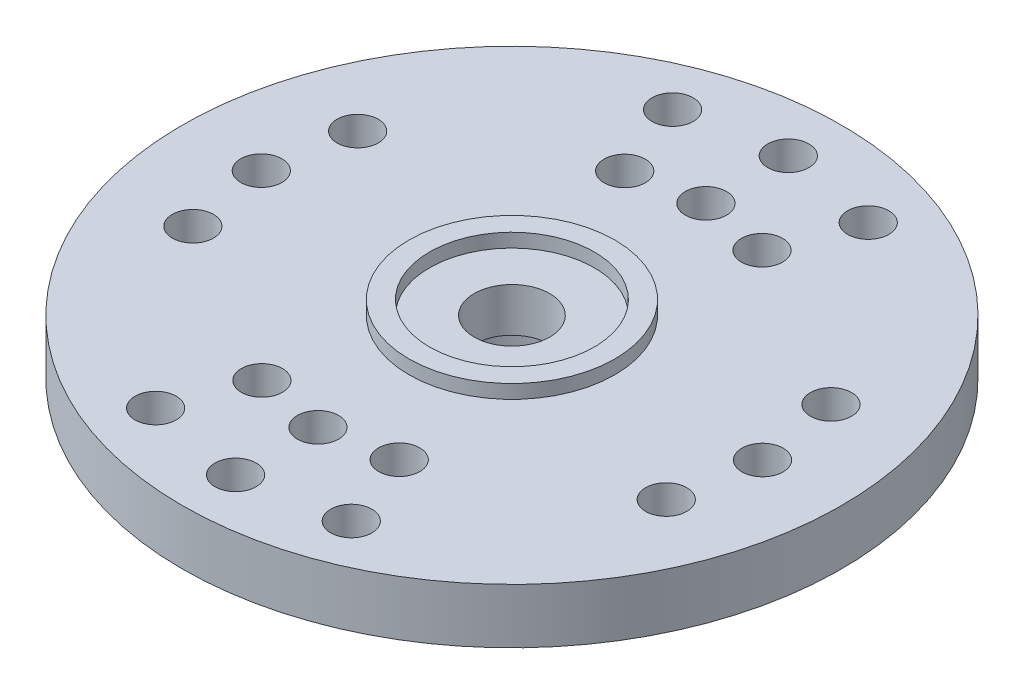
SolidWorks part; units mm, degrees
material "Delrin 2700 NC010, Low Viscosity Acetal Copolymer (SS)"
ref_plane "Front Plane" through (0, 0, 0) normal (0, 0, 1) x (1, 0, 0)
ref_plane "Top Plane" through (0, 0, 0) normal (0, 1, 0) x (1, 0, 0)
ref_plane "Right Plane" through (0, 0, 0) normal (1, 0, 0) x (0, 0, -1)
ref_plane "Plane1" through (0, 0, 0) normal (0, 0, -1) x (-1, 0, 0)
sketch "Sketch1" plane through (0, 0, 0) normal (0, 0, -1) x (-1, 0, 0)
  line L0 (-12, 0) -> (0, 0)
  line L1 (0, 0) -> (0, 2)
  line L2 (0, 2) -> (-12, 2)
  line L3 (-12, 2) -> (-12, 0)
  line L4 (0, 0) -> (0, 2) construction
revolve "Revolve1" add sketch "Sketch1" angle 360 about L4 reverse direction yes
sketch "Sketch2" plane through (0, 0, 0) normal (0, -1, 0) x (1, 0, 0)
  circle A0 centre (0, 0) radius 4.45
extrude "Boss-Extrude1" add sketch "Sketch2" along normal blind 2.6
sketch "Sketch3" plane through (0, 2, 0) normal (0, 1, 0) x (-1, 0, 0)
  circle A0 centre (0, 0) radius 3.75
extrude "Boss-Extrude2" add sketch "Sketch3" along normal blind 0.5
sketch "Sketch4" plane through (0, 0, 0) normal (0, 0, -1) x (-1, 0, 0)
  line L0 (-2.85, -2.6) -> (0, -2.6)
  line L1 (0, -2.6) -> (0, 2.5)
  line L2 (0, 2.5) -> (-3, 2.5)
  line L3 (-3, 2.5) -> (-3, 2)
  line L4 (-3, 2) -> (-1.375, 2)
  line L5 (-1.375, 2) -> (-1.375, 0.4)
  line L6 (-1.375, 0.4) -> (-2.85, 0.4)
  line L7 (-2.85, 0.4) -> (-2.85, -2.6)
  line L8 (0, -2.6) -> (0, 2.5) construction
revolve "Cut-Revolve1" cut sketch "Sketch4" angle 360 about L8 reverse direction yes
hole_wizard "Ø1.5 (1.5) Diameter Hole1" positions "Sketch6" profile "Sketch5" hole size "Ø1.5" standard "ANSI Metric"
sketch "Sketch6" plane through (0, 0, 0) normal (0, -1, 0) x (-1, 0, 0)
  point P0 (-9.125, 0)
  point P1 (9.125, 0)
  point P2 (-8.6178, -3)
  point P3 (-8.6178, 3)
  point P4 (8.6178, -3)
  point P5 (8.6178, 3)
  point P6 (0, 7.0625)
  point P7 (0, -7.0625)
  point P8 (-2.5, 6.6052)
  point P9 (2.5, 6.6052)
  point P10 (-2.5, -6.6052)
  point P11 (2.5, -6.6052)
  point P12 (0, 10.0625)
  point P13 (0, -10.0625)
  point P14 (-3.5619, 9.411)
  point P15 (3.5619, 9.411)
  point P16 (-3.5619, -9.411)
  point P17 (3.5619, -9.411)
sketch "Sketch5" plane through (9.125, 0, 0) normal (1, 0, 0) x (0, 0, -1)
  line L0 (0, 0) -> (0, 2.5)
  line L1 (0, 2.5) -> (0.75, 2.5)
  line L2 (0.75, 2.5) -> (0.75, 0)
  line L5 (0.75, 0) -> (0, 0)
  line L11 (0, -6.35) -> (0, 107.95) construction
  dimension "Thru Hole Dia." = 1.5
  dimension "Thru Hole Depth" = 2.5
